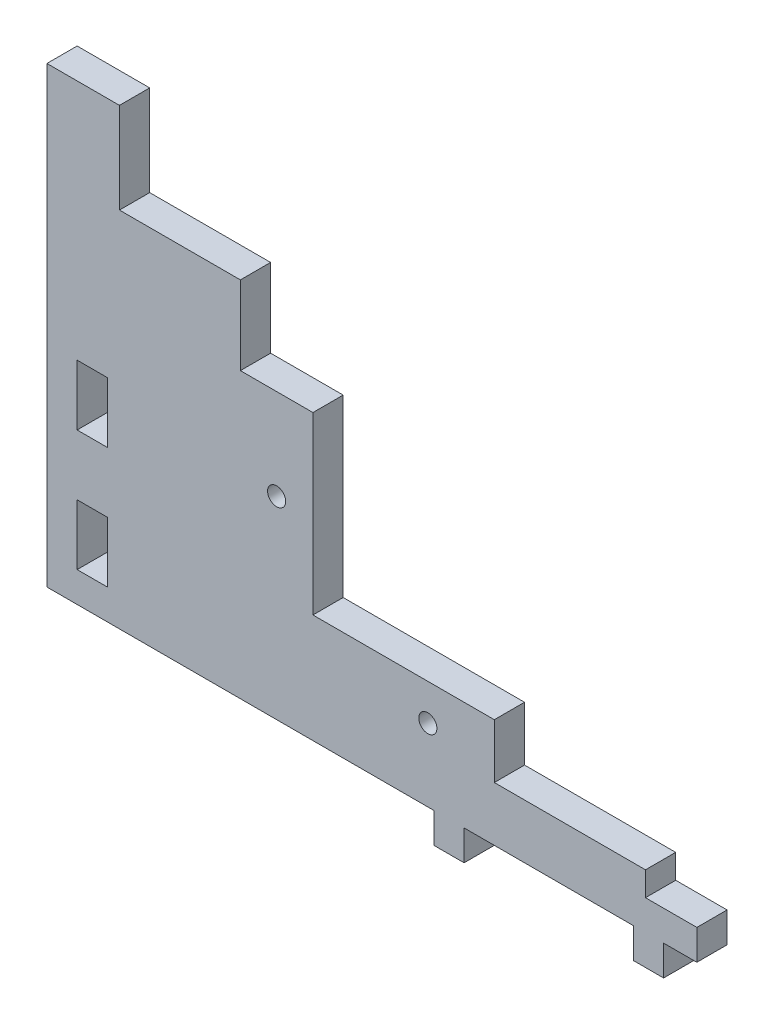
SolidWorks part; units mm, degrees
ref_plane "Plan de face" through (0, 0, 0) normal (0, 0, 1) x (1, 0, 0)
ref_plane "Plan de dessus" through (0, 0, 0) normal (0, 1, 0) x (1, 0, 0)
ref_plane "Plan de droite" through (0, 0, 0) normal (1, 0, 0) x (0, 0, -1)
sketch "Esquisse1" plane through (0, 0, 0) normal (0, 0, 1) x (1, 0, 0)
  line L1 (0, 0) -> (32, 0)
  line L2 (0, 0) -> (0, 47)
  line L3 (0, 47) -> (12, 47)
  line L4 (37, 0) -> (37, 18)
  line L6 (12, 47) -> (12, 18)
  line L7 (12, 18) -> (37, 18)
  line L8 (37, 0) -> (37, -5)
  line L9 (37, -5) -> (32, -5)
  line L10 (32, 0) -> (32, -5)
  circle A0 centre (6, 32) radius 1.5
  circle A1 centre (31, 12) radius 1.5
  dimension "D3" = 20
  dimension "D4" = 3
  dimension "D1" = 6
  dimension "D2" = 12
  dimension "D5" = 15
  dimension "D6" = 6
  dimension "D7" = 25
  dimension "D8" = 6
  dimension "D9" = 6
  dimension "D10" = 5
  dimension "D11" = 5
extrude "Boss.-Extru.1" add sketch "Esquisse1" along normal blind 5
sketch "Esquisse2" plane through (0, 0, 0) normal (0, 0, -1) x (-1, 0, 0)
  line L0 (-37, 18) -> (-12, 18) construction
  line L1 (-37, 0) -> (-65, 0)
  line L2 (-37, 0) -> (-37, 18)
  line L3 (-70, 0) -> (-75.5, 0)
  line L4 (0, 0) -> (32, 0)
  line L5 (0, 20) -> (0, 60)
  line L6 (0, 60) -> (20, 60)
  line L7 (32, 0) -> (32, 75)
  line L8 (0, 0) -> (-32, 0) construction
  line L9 (20, 60) -> (20, 75)
  line L10 (-32, -5) -> (-37, -5) construction
  line L11 (-37, 18) -> (-42, 18)
  line L12 (27, 15) -> (22, 15)
  line L13 (27, 15) -> (27, 5)
  line L14 (27, 5) -> (22, 5)
  line L15 (-70, 0) -> (-70, -5)
  line L16 (-70, -5) -> (-65, -5)
  line L17 (-65, 0) -> (-65, -5)
  line L18 (20, 75) -> (32, 75)
  line L19 (22, 15) -> (22, 5)
  line L20 (27, 35) -> (22, 35)
  line L21 (27, 35) -> (27, 25)
  line L22 (0, 47) -> (0, 0) construction
  line L23 (27, 25) -> (22, 25)
  line L24 (22, 35) -> (22, 25)
  line L25 (-37, 18) -> (-37, 8.7186)
  line L26 (0, 0) -> (-32, 0) construction
  line L27 (-75.5, 5) -> (-67, 5)
  line L28 (-42, 18) -> (-42, 9)
  line L29 (-37, -5) -> (-37, 18) construction
  line L31 (-75.5, 0) -> (-75.5, 5)
  line L32 (-67, 9) -> (-42, 9)
  line L34 (-67, 5) -> (-67, 9)
  circle A0 centre (-31, 12) radius 1.5 construction
  line M2 (0, 0) -> (0, 47)
  line M6 (-37, 18) -> (-37, -5)
  dimension "D1" = 38.5
  dimension "D2" = 20
  dimension "D3" = 28
  dimension "D4" = 5
  dimension "D5" = 10
  dimension "D6" = 5
  dimension "D7" = 15
  dimension "D8" = 10
  dimension "D9" = 5
  dimension "D10" = 32
  dimension "D11" = 11
  dimension "D12" = 5
  dimension "D13" = 60
  dimension "D14" = 25
  dimension "D15" = 40
  dimension "D16" = 5
  dimension "D17" = 3
extrude "Boss.-Extru.2" add sketch "Esquisse2" against normal blind 5 contours L18 L9 L6 L5 L4 M2 | L1 M6 region at (53.6814, 4.8791, 0) region at (-16.475, 33.875, 0)
